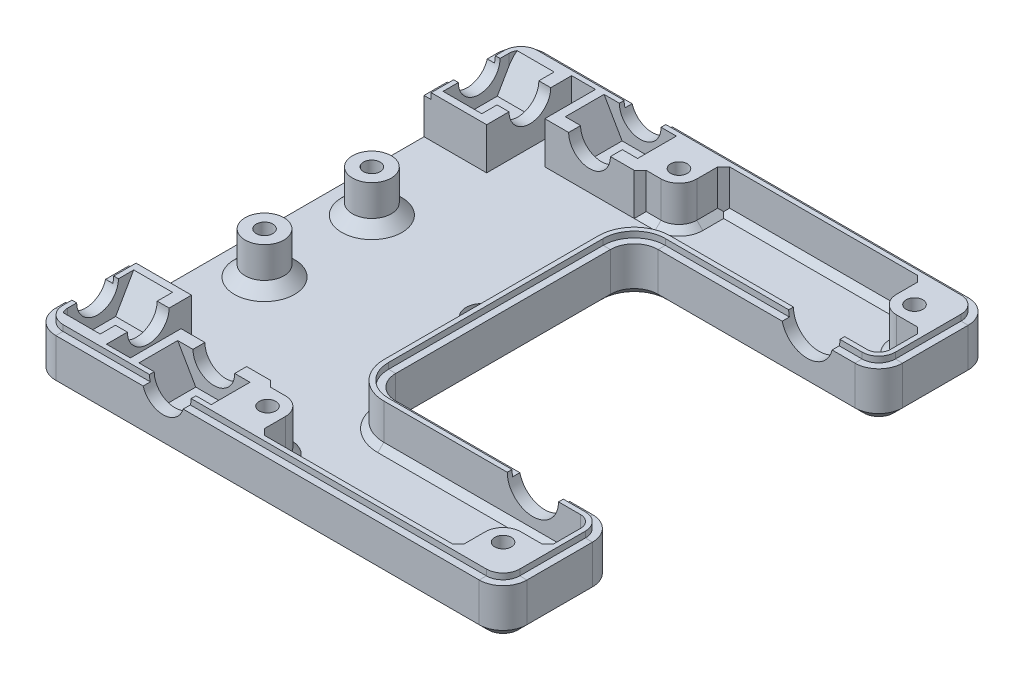
SolidWorks part; units mm, degrees
ref_plane "Front Plane" through (0, 0, 0) normal (0, 0, 1) x (1, 0, 0)
ref_plane "Top Plane" through (0, 0, 0) normal (0, 1, 0) x (1, 0, 0)
ref_plane "Right Plane" through (0, 0, 0) normal (1, 0, 0) x (0, 0, -1)
sketch "Sketch1" plane through (0, 0, 0) normal (0, 1, 0) x (1, 0, 0)
  line L1 (4, 22) -> (37, 22)
  line L2 (41, 26) -> (41, 37)
  line L3 (37, 41) -> (-34, 41)
  line L4 (-38, 37) -> (-38, -37)
  line L5 (-34, -41) -> (37, -41)
  line L6 (41, -37) -> (41, -26)
  line L7 (37, -22) -> (4, -22)
  line L9 (0, 18) -> (0, -18)
  arc A0 (41, 37) -> (37, 41) centre (37, 37) ccw
  arc A1 (37, 22) -> (41, 26) centre (37, 26) ccw
  arc A2 (37, -41) -> (41, -37) centre (37, -37) ccw
  arc A3 (41, -26) -> (37, -22) centre (37, -26) ccw
  arc A4 (4, -22) -> (0, -18) centre (4, -18) cw
  arc A5 (0, 18) -> (4, 22) centre (4, 18) cw
  arc A6 (-34, 41) -> (-38, 37) centre (-34, 37) ccw
  arc A7 (-38, -37) -> (-34, -41) centre (-34, -37) ccw
  point P0 (0, 0)
  point P13 (41, 41)
  point P16 (41, 22)
  point P23 (0, -22)
  point P26 (0, 22)
  dimension "D5" = 4
  dimension "D1" = 44
  dimension "D2" = 41
  dimension "D3" = 19
  dimension "D4" = 38
extrude "Boss-Extrude1" add sketch "Sketch1" along normal blind 9
shell "Shell1" thickness 2 removed face at (11, 9, 0)
sketch "Esboço5" plane through (0, 0, 0) normal (0, 0, 1) x (1, 0, 0)
  line L0 (-38, 9) -> (-36.8, 9)
  line L1 (-36.8, 9) -> (-36.8, 8)
  line L2 (-36.8, 8) -> (-38, 8)
  line L3 (-38, 8) -> (-38, 9)
  dimension "D1" = 1
  dimension "D2" = 1.2
sketch "Esboço6" plane through (0, 9, 0) normal (0, 1, 0) x (1, 0, 0)
  line L8 (37, 41) -> (-34, 41)
  line L9 (-38, 37) -> (-38, -37)
  line L10 (-34, -41) -> (37, -41)
  line L11 (41, -37) -> (41, -26)
  line L12 (37, -22) -> (4, -22)
  line L13 (0, -18) -> (0, 18)
  line L14 (4, 22) -> (37, 22)
  line L15 (41, 26) -> (41, 37)
  line L16 (37, 41) -> (-34, 41)
  line L17 (-38, 37) -> (-38, -37)
  line L18 (-34, -41) -> (37, -41)
  line L19 (41, -37) -> (41, -26)
  line L20 (37, -22) -> (4, -22)
  line L21 (0, -18) -> (0, 18)
  line L22 (4, 22) -> (37, 22)
  line L23 (41, 26) -> (41, 37)
  arc A8 (41, 37) -> (37, 41) centre (37, 37) ccw
  arc A9 (-34, 41) -> (-38, 37) centre (-34, 37) ccw
  arc A10 (-38, -37) -> (-34, -41) centre (-34, -37) ccw
  arc A11 (37, -41) -> (41, -37) centre (37, -37) ccw
  arc A12 (41, -26) -> (37, -22) centre (37, -26) ccw
  arc A13 (0, -18) -> (4, -22) centre (4, -18) ccw
  arc A14 (4, 22) -> (0, 18) centre (4, 18) ccw
  arc A15 (37, 22) -> (41, 26) centre (37, 26) ccw
  arc A16 (41, 37) -> (37, 41) centre (37, 37) ccw
  arc A17 (-34, 41) -> (-38, 37) centre (-34, 37) ccw
  arc A18 (-38, -37) -> (-34, -41) centre (-34, -37) ccw
  arc A19 (37, -41) -> (41, -37) centre (37, -37) ccw
  arc A20 (41, -26) -> (37, -22) centre (37, -26) ccw
  arc A21 (0, -18) -> (4, -22) centre (4, -18) ccw
  arc A22 (4, 22) -> (0, 18) centre (4, 18) ccw
  arc A23 (37, 22) -> (41, 26) centre (37, 26) ccw
  dimension "D1" = 0
chamfer "Chamfer1" distance 1 angle 45 16 edges at (-35.4142, 2, 38.4142) (-36, 2, 0) (-35.4142, 2, -38.4142) (1.5, 2, -39) (38.4142, 2, -38.4142) (39, 2, -31.5) (38.4142, 2, -24.5858) (20.5, 2, -24) (-0.2426, 2, -22.2426) (-2, 2, 0) (-0.2426, 2, 22.2426) (20.5, 2, 24) (38.4142, 2, 24.5858) (39, 2, 31.5) (38.4142, 2, 38.4142) (1.5, 2, 39)
sketch "Sketch6" plane through (0, 0, 0) normal (0, 0, 1) x (1, 0, 0)
  line L0 (41, 9) -> (41, 0) construction
  line L1 (-34, 9) -> (37, 9) construction
  circle A0 centre (29, 9) radius 4.3
  dimension "D2" = 8.6
  dimension "D1" = 12
sketch "Esboço3" plane through (-38, 0, 0) normal (-1, 0, 0) x (0, 0, 1)
  line L1 (-24.75, 2) -> (24.75, 2)
  line L2 (-24.75, 2) -> (-24.75, 16)
  line L3 (-24.75, 16) -> (24.75, 16)
  line L4 (24.75, 2) -> (24.75, 16)
  line L5 (-37, 9) -> (37, 9) construction
  point P6 (0, 16)
  point P9 (24.75, 9)
  dimension "D1" = 49.5
  dimension "D2" = 14
sweep "Varredura de corte2" cut profiles "Esboço5" path "Esboço6"
extrude "Cut-Extrude1" cut sketch "Sketch6" along normal blind 27 and the other way blind 27 contours A0 region at (29, 9, 0)
sketch "Sketch9" plane through (0, 0, 41) normal (0, 0, 1) x (1, 0, 0)
  line L0 (-34, 9) -> (37, 9) construction
  line L1 (-12.9689, 3.75) -> (-9.9378, 9)
  line L2 (-9.9378, 9) -> (-12.9689, 14.25)
  line L3 (-12.9689, 14.25) -> (-19.0311, 14.25)
  line L4 (-19.0311, 14.25) -> (-22.0622, 9)
  line L5 (-22.0622, 9) -> (-19.0311, 3.75)
  line L6 (-19.0311, 3.75) -> (-12.9689, 3.75)
  line L7 (-23.5, 9) -> (-8.5, 9)
  line L8 (-38, 8) -> (-38, 0) construction
  line L10 (-23.5, 16) -> (-8.5, 16)
  line L11 (-23.5, 16) -> (-23.5, 2)
  line L12 (-23.5, 2) -> (-8.5, 2)
  line L13 (-8.5, 16) -> (-8.5, 2)
  line L14 (-23.5, 16) -> (-8.5, 2) construction
  line L15 (-23.5, 2) -> (-8.5, 16) construction
  line L16 (38, 2) -> (37, 2) construction
  circle A0 centre (-16, 9) radius 5.25 construction
  circle A2 centre (-16, 9) radius 3.5
  line M26 (37, 8) -> (-34, 8)
  dimension "D2" = 15
  dimension "D4" = 7
  dimension "D1" = 10.5
  dimension "D3" = 22
extrude "Boss-Extrude6" add sketch "Sketch9" against normal blind 6.5 from offset 2 contours L13 L1 L6 L5 L11 | L7 L11 L5 M26 | L13 L7 L1 M26 region at (-11.6021, 5.7942, 41) region at (-9.3713, 8.4721, 41) region at (-22.6287, 8.4721, 41) offset against normal yes
extrude "Boss-Extrude7" add sketch "Sketch9<4>" against normal blind 2 from surface contours L13 L1 L6 L5 L11 | A2 L5 L6 L1 | L7 L11 L5 M26 | A2 L7 L5 M26 | L13 L7 L1 M26 | A2 L1 L7 M26 region at (-16, 3.8676, 41) region at (-11.6021, 5.7942, 41) region at (-11.3818, 8.5155, 41) region at (-9.3713, 8.4721, 41) region at (-22.6287, 8.4721, 41) region at (-20.6182, 8.5155, 41) starting at face at (-16, 5.9375, 32.5)
sketch "Sketch9<4>" plane through (0, 0, 41) normal (0, 0, 1) x (1, 0, 0) same geometry as "Sketch9"
mirror "Mirror5" about plane through (0, 0, 0) normal (0, 0, 1) of "Boss-Extrude6"
extrude "Boss-Extrude8" add sketch "Sketch9<5>" along normal blind 2 from surface contours L13 L1 L6 L5 L11 | A2 L5 L6 L1 | L13 L7 L1 M26 | A2 L1 L7 M26 | A2 L7 L5 M26 | L7 L11 L5 M26 region at (-16, 3.8676, 41) region at (-11.6021, 5.7942, 41) region at (-11.3818, 8.5155, 41) region at (-9.3713, 8.4721, 41) region at (-22.6287, 8.4721, 41) region at (-20.6182, 8.5155, 41) starting at face at (-16, 5.9375, -32.5)
sketch "Sketch9<5>" plane through (0, 0, 41) normal (0, 0, 1) x (1, 0, 0) same geometry as "Sketch9"
extrude "Cut-Extrude3" cut sketch "Sketch9<3>" against normal through all contours L7 A2 | A2 M26 region at (-16, 8.5035, 41) region at (-16, 6.9612, 41)
sketch "Sketch9<3>" plane through (0, 0, 41) normal (0, 0, 1) x (1, 0, 0) same geometry as "Sketch9"
sketch "Sketch10" plane through (-38, 0, 0) normal (-1, 0, 0) x (0, 0, 1)
  line L6 (24.5, 9) -> (39.5, 9)
  line L7 (24.5, 16) -> (39.5, 16)
  line L8 (24.5, 16) -> (24.5, 2)
  line L9 (24.5, 2) -> (39.5, 2)
  line L10 (39.5, 16) -> (39.5, 2)
  line L11 (24.5, 16) -> (39.5, 2) construction
  line L12 (24.5, 2) -> (39.5, 16) construction
  line L13 (41, 8) -> (41, 0) construction
  line L14 (35.0311, 14.25) -> (28.9689, 14.25)
  line L15 (28.9689, 14.25) -> (25.9378, 9)
  line L16 (25.9378, 9) -> (28.9689, 3.75)
  line L17 (28.9689, 3.75) -> (35.0311, 3.75)
  line L18 (35.0311, 3.75) -> (38.0622, 9)
  line L19 (38.0622, 9) -> (35.0311, 14.25)
  line L20 (-30.5, 2) -> (-38, 2) construction
  line L23 (37, 9) -> (0, 9) construction
  circle A1 centre (32, 9) radius 3.5
  circle A2 centre (32, 9) radius 5.25 construction
  line M20 (37, 0) -> (37, 8)
  line M43 (37, 8) -> (0, 8)
  dimension "D3" = 7
  dimension "D1" = 10.5
  dimension "D2" = 15
  dimension "D4" = 9
extrude "Boss-Extrude9" add sketch "Sketch10" along normal up to body from offset 10.5 separate body contours L18 L17 L16 L6 L8 L10 | L18 L9 L10 L6 M20 | L16 L6 L8 M43 region at (-38, 8.4721, 25.3713) region at (-38, 7.8613, 25.5076) region at (-38, 5.3293, 38.303) offset against normal yes
extrude "Boss-Extrude10" add sketch "Sketch10<3>" along normal blind 2 from surface contours L18 L17 L16 L6 L8 L10 | L18 L9 L10 L6 M20 | A1 L16 L17 L18 M20 | L18 L6 M20 | A1 L6 L16 M43 | L16 L6 L8 M43 region at (-38, 8.4721, 25.3713) region at (-38, 8.5155, 27.3818) region at (-38, 7.8613, 25.5076) region at (-38, 7.8869, 27.5805) region at (-38, 8.4514, 36.662) region at (-38, 5.3293, 38.303) starting at face at (-27.5, 5.6111, 32.5556)
sketch "Sketch10<3>" plane through (-38, 0, 0) normal (-1, 0, 0) x (0, 0, 1) same geometry as "Sketch10"
extrude "Cut-Extrude4" cut sketch "Sketch10<4>" against normal blind 11 contours A1
sketch "Sketch10<4>" plane through (-38, 0, 0) normal (-1, 0, 0) x (0, 0, 1) same geometry as "Sketch10"
mirror "Mirror6" about plane through (0, 0, 0) normal (0, 0, 1) of "Cut-Extrude4", "Boss-Extrude10", "Boss-Extrude9"
sketch "Esboço1" plane through (0, 0, 0) normal (0, -1, 0) x (1, 0, 0)
  line L0 (-23, -25.9392) -> (-23, 25.9392) construction
  line L1 (-12, -30.0516) -> (-12, 30.0516) construction
  line L2 (-18.6273, 4.1566) -> (-18.6273, 4.9624)
  line L3 (-18.6273, 4.9624) -> (-20.109, 5.9391)
  line L4 (-20.109, 5.9391) -> (-20.109, 5.1333)
  line L5 (-20.109, 5.1333) -> (-18.6273, 4.1566)
  text T0 "<i>DFTE</i>" font "@Adobe Gothic Std B" height 9
  text T1 "<b>SENSOR OPTICO</b>" font "@Adobe Gothic Std B" height 6
  point P5 (-23, 0)
  point P6 (-12, 0)
  point P13 (0, 0)
  point P14 (-19.764, 5.3906)
  point P15 (-18.4802, 4.7167)
  point P16 (-19.9383, 5.7897)
  point P17 (-18.4425, 4.8285)
  point P19 (-18.4425, 3.9695)
  point P20 (-20.1497, 5.9156)
  point P21 (-20.109, 4.8952)
  point P22 (-18.4425, 4.8944)
  point P23 (-20.109, 5.5362)
  point P24 (-18.6273, 4.9624)
  dimension "D1" = 23
  dimension "D2" = 12
extrude "Corte-extrusão1" cut sketch "Esboço1" against normal blind 0.7
sketch "Esboço2" plane through (0, 2, 0) normal (0, 1, 0) x (1, 0, 0)
  line L1 (0, -18) -> (0, 18) construction
  line L2 (37, 41) -> (-19.5, 41) construction
  circle A0 centre (-7, 3.5) radius 2.7
  dimension "D3" = 5.4
  dimension "D1" = 37.5
  dimension "D2" = 7
extrude "Corte-extrusão2" cut sketch "Esboço2" against normal blind 10 contours A0
extrude "Corte-extrusão3" cut sketch "Esboço3" against normal blind 12
sketch "Esboço4" plane through (0, 2, 0) normal (0, 1, 0) x (1, 0, 0)
  line L0 (-2, 34.5) -> (-2, 39)
  line L1 (37, 39) -> (-8.5, 39) construction
  line L2 (-2, 39) -> (-8.5, 39)
  line L3 (0, 0) -> (-38, 0) construction
  line L4 (31.5, 34.5) -> (31.5, 39)
  line L5 (34.5, 31.5) -> (39, 31.5)
  line L6 (39, 26) -> (39, 37) construction
  line L7 (39, 31.5) -> (39, 37)
  line L8 (37, 39) -> (31.5, 39)
  line L9 (37, -39) -> (31.5, -39)
  line L10 (39, -31.5) -> (39, -37)
  line L11 (34.5, -31.5) -> (39, -31.5)
  line L12 (31.5, -34.5) -> (31.5, -39)
  line L13 (-5, 31.5) -> (-8.5, 31.5)
  line L14 (-2, -39) -> (-8.5, -39)
  line L15 (-2, -34.5) -> (-2, -39)
  line L16 (-5, -31.5) -> (-8.5, -31.5)
  line L18 (-8.5, -31.5) -> (-8.5, -39)
  line L19 (-8.5, 30.5) -> (-8.5, 38) construction
  line L20 (-8.5, 31.5) -> (-8.5, 39)
  line L21 (41, 26) -> (41, 37) construction
  line L22 (37, 41) -> (-19.5, 41) construction
  line L23 (-38, 24.75) -> (-38, -24.75) construction
  line L24 (37, -39) -> (-8.5, -39) construction
  line L25 (39, -26) -> (39, -37) construction
  arc A17 (39, 37) -> (37, 39) centre (37, 37) ccw construction
  arc A18 (39, 37) -> (37, 39) centre (37, 37) ccw
  arc A19 (37, -39) -> (39, -37) centre (37, -37) ccw construction
  circle A20 centre (-31, 34.5) radius 3 construction
  circle A21 centre (34.5, 34.5) radius 3
  circle A22 centre (-31, -34.5) radius 3 construction
  circle A23 centre (34.5, -34.5) radius 3
  circle A24 centre (-31, 34.5) radius 1.4 construction
  circle A25 centre (34.5, 34.5) radius 1.4
  circle A26 centre (-31, -34.5) radius 1.4 construction
  circle A27 centre (34.5, -34.5) radius 1.4
  circle A28 centre (-31, 9) radius 3.25
  circle A29 centre (-31, 9) radius 1.4
  circle A30 centre (-31, -9) radius 1.4
  circle A31 centre (-31, -9) radius 3.25
  circle A32 centre (-5, 34.5) radius 1.4
  circle A33 centre (-5, -34.5) radius 3
  circle A34 centre (-5, -34.5) radius 1.4
  circle A35 centre (-5, 34.5) radius 3
  arc A36 (37, -39) -> (39, -37) centre (37, -37) ccw
  point P15 (-31, -5.75)
  point P49 (-31, 5.75)
  point P53 (-31, -12.25)
  point P71 (0, 0)
  point P74 (-27.75, 9)
  point P89 (-34, 9)
  line M27 (-8.5, -38) -> (37, -38)
  arc M28 (37, -38) -> (38, -37) centre (37, -37) ccw
  line M29 (38, -37) -> (38, -26)
  line M37 (38, 26) -> (38, 37)
  arc M38 (38, 37) -> (37, 38) centre (37, 37) ccw
  line M39 (37, 38) -> (-8.5, 38)
  dimension "D1" = 6.5
  dimension "D5" = 2.8
  dimension "D6" = 6
  dimension "D2" = 3.5
  dimension "D3" = 6.5
  dimension "D4" = 6.5
  dimension "D7" = 18
  dimension "D8" = 7
extrude "Ressalto-extrusão1" add sketch "Esboço4" along normal blind 7 contours A35 A32 | A21 A25 | A33 A34 | A23 A27 | A31 A30 | A28 A29 region at (-2.9387, 2, -32.4387) region at (34.5, 2, -37.4151) region at (32.4387, 2, 32.4387) region at (-7.0613, 2, 36.5613) region at (-34.1581, 2, -9) region at (-34.1581, 2, 9)
chamfer "Chanfro1" distance 1.8 angle 45 2 edges at (-31, 2, -5.75) (-31, 2, 12.25)
extrude "Ressalto-extrusão2" add sketch "Esboço4<2>" along normal up to surface (7 mm away) contours A35 L0 M39 | A21 L5 L4 M37 M38 M39 | L10 L11 L12 L9 M29 M28 M27 | A33 L15 M27 | A23 L12 L11 M27 M28 M29 | L15 L14 M27 | L2 L0 M39 | L7 A18 L8 L4 L5 M39 M38 M37 region at (-7.1863, 2, -36.6863) region at (31.6061, 2, -38.5) region at (34.25, 2, -37.9081) region at (-5.25, 2, -38.5) region at (-5.25, 2, 38.5) region at (-5.25, 2, 37.9081) region at (34.25, 2, 38.8939) region at (31.5919, 2, 36.25) up to face at (15.9618, 9, 32.3333)
sketch "Esboço4<2>" plane through (0, 2, 0) normal (0, 1, 0) x (1, 0, 0) same geometry as "Esboço4"
chamfer "Chanfro2" distance 1 angle 45 20 edges at (39, 6, -31.5) (31.5, 6, -39) (36.25, 2, -31.5) (32.3787, 2, -32.3787) (31.5, 2, -36.25) (-2, 6, -39) (-2, 2, -36.25) (-2.8787, 2, -32.3787) (39, 6, 31.5) (31.5, 6, 39) (31.5, 2, 36.25) (32.3787, 2, 32.3787) (36.25, 2, 31.5) (-2.8787, 2, 32.3787) (-2, 2, 36.25) (-2, 6, 39) (-6.75, 2, -31.5) (-6.75, 2, 31.5) (-8.5, 5.5, 31.5) (-8.5, 5.5, -31.5)
chamfer "Chanfro3" distance 1.5 angle 45 16 edges at (20.5, 0, 22) (1.1716, 0, 20.8284) (39.8284, 0, 23.1716) (0, 0, 0) (41, 0, 31.5) (1.1716, 0, -20.8284) (39.8284, 0, 39.8284) (20.5, 0, -22) (1.5, 0, 41) (39.8284, 0, -23.1716) (-36.8284, 0, 39.8284) (41, 0, -31.5) (-38, 0, 0) (39.8284, 0, -39.8284) (-36.8284, 0, -39.8284) (1.5, 0, -41)
